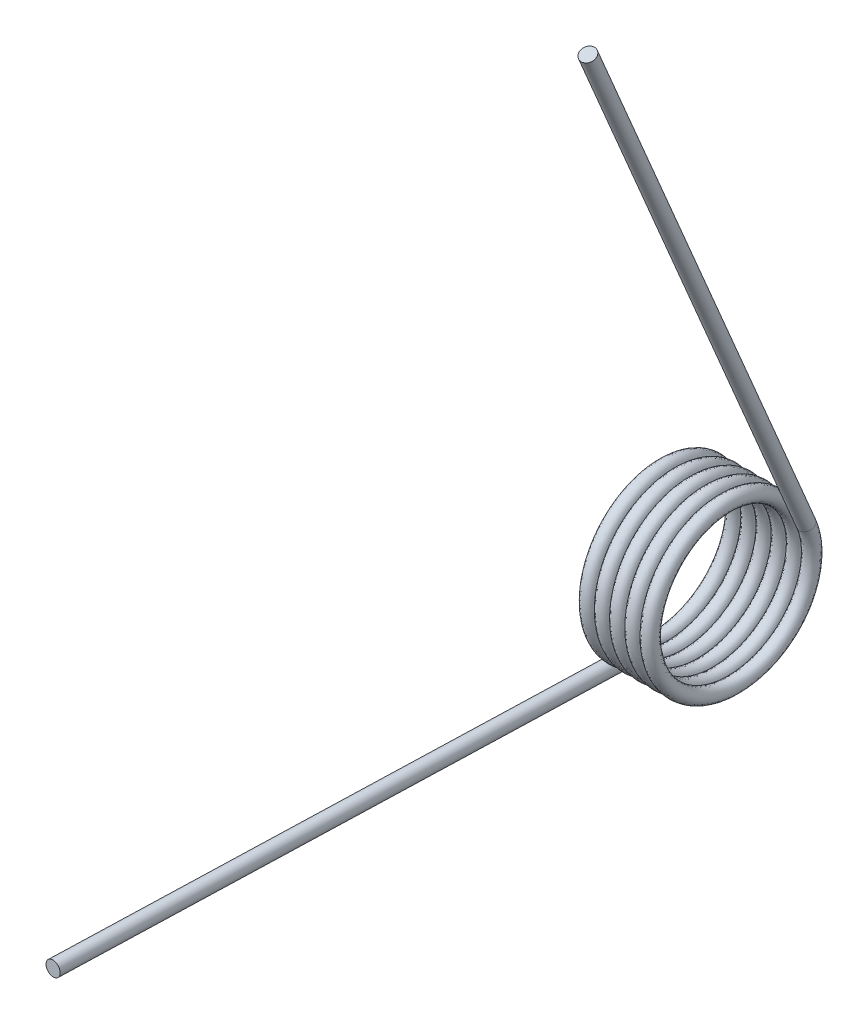
SolidWorks part; units mm, degrees
ref_plane "xy_plane" through (0, 0, 0) normal (0, 0, 1) x (1, 0, 0)
ref_plane "zx_plane" through (0, 0, 0) normal (0, 1, 0) x (1, 0, 0)
ref_plane "yz_plane" through (0, 0, 0) normal (1, 0, 0) x (0, 0, -1)
ref_axis "x_axis" through (-1.3397, 0, 0) along (1, 0, 0)
ref_axis "y_axis" through (0, -4.2648, 0) along (0, 1, 0)
ref_axis "z_axis" through (0, 0, -27.9381) along (0, 0, 1)
sketch "Sketch1" plane through (0, 0, 0) normal (1, 0, 0) x (0, 0, -1)
  line L0 (0, 0) -> (0, -3.0267) construction
  line L1 (0, -3.0267) -> (0, -3.3442) construction
  line L2 (0, -3.3442) -> (0, -3.6617) construction
  circle A0 centre (0, 0) radius 3.0267 construction
  circle A1 centre (0, 0) radius 3.6617 construction
  circle A2 centre (0, 0) radius 3.3442
  circle A3 centre (0, -3.3442) radius 0.3175 construction
  circle A4 centre (0, 0) radius 2.5781 construction
sketch "turningAngleFollower_sketch" plane through (0, 0, 0) normal (1, 0, 0) x (0, 0, -1)
  line L0 (3.0607, 1.3474) -> (-7.1734, 24.5944)
  line L1 (27.9381, 0) -> (-27.9381, 0) construction
  circle A0 centre (0, 0) radius 3.3442 construction
  circle A1 centre (-4.9342, 24.0971) radius 1.849 construction
  point P2 (0, 0)
  point P4 (23.3879, 9.908)
  point P7 (17.2581, 18.6365)
  point P8 (3.2712, -3.8533)
  point P9 (0, 0)
  dimension "D1" = 25.4
  dimension "turningAngle" = 113.761
curve "Helix/Spiral1" pitch 0.6604 height 3.511 radius 3.3442 centre (0, 0, 0) axis (1, 0, 0) start towards (0, 0, -1) parameters "height"=3.511, "pitch"=0.6604
ref_plane "Plane1" through (0, -3.3442, 0) normal (0.0314, 0, -0.9995) x (-0.9995, 0, -0.0314)
sketch "Sketch2" plane through (0, -3.3442, 0) normal (0.0314, 0, -0.9995) x (-0.9995, 0, -0.0314)
  circle A0 centre (0, 0) radius 0.3175
  dimension "D1" = 0.635
sweep "Sweep1" add profiles "Sketch2" path "Helix/Spiral1"
sketch "Sketch3" plane through (0, 0, 0) normal (-0.0314, 0, 0.9995) x (0.9995, 0, 0.0314)
  circle A1 centre (0, -3.3442) radius 0.3175
  circle A2 centre (0, -3.3442) radius 0.3175
  dimension "D1" = 0
extrude "Extrude1" add sketch "Sketch3" along normal blind 25.4
sketch "Sketch4" plane through (0.0035, 0.1008, 0.0447) normal (0.0314, 0.9137, 0.4051) x (0.4944, 0.338, -0.8008)
  circle A1 centre (4.6422, -1.3957) radius 0.3175
  circle A2 centre (4.6422, -1.3957) radius 0.3175
  dimension "D1" = 0
extrude "Extrude2" add sketch "Sketch4" along normal blind 25.4
sketch "Sketch5" plane through (0, 0, 0) normal (1, 0, 0) x (0, 0, -1)
  circle A0 centre (0, 0) radius 2.5781 construction
  circle A1 centre (0, 0) radius 2.5781
equation "\"pitch@Helix/Spiral1\"= \"helixPitch\""
equation "\"D1@Sketch2\" = \"wireDiameter\""
equation "\"D1@Extrude2\"=\"Leg Length@Extrude1\""
equation "\"wireDiameter\"= 0.025in"
equation "\"relaxedNumberOfTurns\"= 5"
equation "\"relaxedHelixDiameter\" = \"relaxedSpringOD\" - \"wireDiameter\""
equation "\"relaxedSpringOD\"= 0.305in"
equation "\"helixLength\" = \"relaxedNumberOfTurns\" * sqr ( ( PI * \"relaxedHelixDiameter\" ) ^ 2 + \"helixPitch\" ^ 2 )"
equation "\"helixPitch\" = \"wireDiameter\" + 0.001in"
equation "\"numberOfTurns\"= \"relaxedNumberOfTurns\" + \"turningAngle\" / 360deg"
equation "\"helixDiameter\"= 1 / PI * sqr ( ( \"helixLength\" / \"numberOfTurns\" ) ^ 2 - \"helixPitch\" ^ 2 )"
equation "\"springOD\"= \"helixDiameter\" + \"wireDiameter\""
equation "\"Spring OD@Sketch1\"= \"springOD\""
equation "\"Wire Dia@Sketch1\"= \"wireDiameter\""
equation "\"Number Coils@Helix/Spiral1\"= \"numberOfTurns\""
equation "\"turningAngle\"= \"turningAngle@turningAngleFollower_sketch\""
